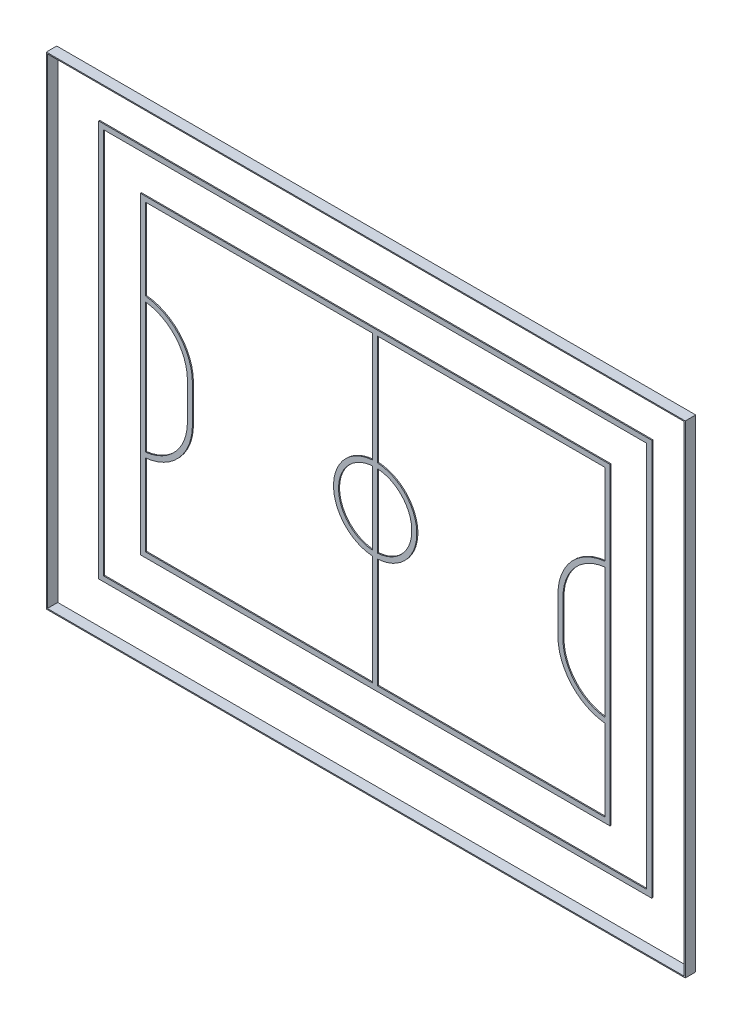
SolidWorks part; units mm, degrees
note: The reader was unsure of these and kept them because the rebuilt part matched: shared geometry of "Sketch1<3>".
ref_plane "Front Plane" through (0, 0, 0) normal (0, 0, 1) x (1, 0, 0)
ref_plane "Top Plane" through (0, 0, 0) normal (0, 1, 0) x (1, 0, 0)
ref_plane "Right Plane" through (0, 0, 0) normal (1, 0, 0) x (0, 0, -1)
sketch "Sketch1" plane through (0, 0, 0) normal (0, 0, 1) x (1, 0, 0)
  line L0 (-2250, 1500) -> (2250, 1500)
  line L1 (2250, -1500) -> (2250, 1500)
  line L2 (-2250, -1500) -> (2250, -1500)
  line L3 (-2250, -1500) -> (-2250, 1500)
  line L4 (-2251, 1501) -> (2251, 1501)
  line L5 (-2251, -1501) -> (-2251, 1501)
  line L6 (-2251, -1501) -> (2251, -1501)
  line L7 (2251, -1501) -> (2251, 1501)
  line L8 (-2200, 672.4937) -> (-2200, 1450)
  line L9 (-2200, 1450) -> (-25, 1450)
  line L10 (-25, 399.218) -> (-25, 1450)
  line L11 (-25, -1450) -> (-25, -399.218)
  line L12 (-2200, -1450) -> (-25, -1450)
  line L13 (-2200, -1450) -> (-2200, -672.4937)
  line L14 (-1750, -175) -> (-1750, 175)
  line L15 (-1751, -175) -> (-1751, 175)
  line L16 (-2201, -1451) -> (-2201, -671.5884)
  line L17 (-2201, -1451) -> (-24, -1451)
  line L18 (-24, -1451) -> (-24, -398.2775)
  line L19 (-24, 398.2775) -> (-24, 1451)
  line L20 (-2201, 1451) -> (-24, 1451)
  line L21 (-2201, 671.5884) -> (-2201, 1451)
  line L22 (-1799, -175) -> (-1799, 175)
  line L23 (-2201, -623.3302) -> (-2201, 623.3302)
  line L24 (-1800, -175) -> (-1800, 175)
  line L25 (-2200, -622.2136) -> (-2200, 622.2136)
  line L26 (-24, -350.1785) -> (-24, 350.1785)
  line L27 (-25, -349.106) -> (-25, 349.106)
  line L28 (25, -349.106) -> (25, 349.106)
  line L29 (24, -350.1785) -> (24, 350.1785)
  line L30 (2201, -1451) -> (2201, -671.5884)
  line L31 (1751, -175) -> (1751, 175)
  line L32 (2201, 671.5884) -> (2201, 1451)
  line L33 (24, 1451) -> (2201, 1451)
  line L34 (24, 398.2775) -> (24, 1451)
  line L35 (24, -1451) -> (24, -398.2775)
  line L36 (24, -1451) -> (2201, -1451)
  line L37 (2200, -1450) -> (2200, -672.4937)
  line L38 (25, -1450) -> (2200, -1450)
  line L39 (25, -1450) -> (25, -399.218)
  line L40 (25, 399.218) -> (25, 1450)
  line L41 (25, 1450) -> (2200, 1450)
  line L42 (2200, 672.4937) -> (2200, 1450)
  line L43 (1750, -175) -> (1750, 175)
  line L44 (2200, -622.2136) -> (2200, 622.2136)
  line L45 (1800, -175) -> (1800, 175)
  line L46 (1799, -175) -> (1799, 175)
  line L47 (2201, -623.3302) -> (2201, 623.3302)
  line L48 (-2600, 1850) -> (2600, 1850)
  line L49 (2600, -1850) -> (2600, 1850)
  line L50 (-2600, -1850) -> (2600, -1850)
  line L51 (-2600, -1850) -> (-2600, 1850)
  line L52 (-2601, 1851) -> (2601, 1851)
  line L53 (-2601, -1851) -> (-2601, 1851)
  line L54 (-2601, -1851) -> (2601, -1851)
  line L55 (2601, -1851) -> (2601, 1851)
  line L56 (-2650, 1900) -> (2650, 1900)
  line L57 (2650, -1900) -> (2650, 1900)
  line L58 (-2650, -1900) -> (2650, -1900)
  line L59 (-2650, -1900) -> (-2650, 1900)
  line L60 (-2651, 1901) -> (2651, 1901)
  line L61 (-2651, -1901) -> (-2651, 1901)
  line L62 (-2651, -1901) -> (2651, -1901)
  line L63 (2651, -1901) -> (2651, 1901)
  line L64 (-3050, -2300) -> (3050, -2300)
  line L65 (-3050, -2300) -> (-3050, 2300)
  line L66 (-3050, 2300) -> (3050, 2300)
  line L67 (3050, -2300) -> (3050, 2300)
  line L68 (-3051, -2301) -> (-3051, 2301)
  line L69 (-3051, -2301) -> (3051, -2301)
  line L70 (3051, -2301) -> (3051, 2301)
  line L71 (-3051, 2301) -> (3051, 2301)
  line L72 (-3061, -2311) -> (-3061, 2311)
  line L73 (-3061, 2311) -> (3061, 2311)
  line L74 (3061, -2311) -> (3061, 2311)
  line L75 (-3061, -2311) -> (3061, -2311)
  arc A0 (-1750, 175) -> (-2200, 672.4937) centre (-2250, 175) ccw
  arc A1 (-25, 399.218) -> (-25, -399.218) centre (0, 0) ccw
  arc A2 (-2200, -672.4937) -> (-1750, -175) centre (-2250, -175) ccw
  arc A3 (-1751, 175) -> (-2201, 671.5884) centre (-2250, 175) ccw
  arc A4 (-2201, -671.5884) -> (-1751, -175) centre (-2250, -175) ccw
  arc A5 (-24, 398.2775) -> (-24, -398.2775) centre (0, 0) ccw
  arc A6 (-1799, 175) -> (-2201, 623.3302) centre (-2250, 175) ccw
  arc A7 (-2201, -623.3302) -> (-1799, -175) centre (-2250, -175) ccw
  arc A8 (-1800, 175) -> (-2200, 622.2136) centre (-2250, 175) ccw
  arc A9 (-2200, -622.2136) -> (-1800, -175) centre (-2250, -175) ccw
  arc A10 (-24, 350.1785) -> (-24, -350.1785) centre (0, 0) ccw
  arc A11 (-25, 349.106) -> (-25, -349.106) centre (0, 0) ccw
  arc A12 (25, -349.106) -> (25, 349.106) centre (0, 0) ccw
  arc A13 (24, -350.1785) -> (24, 350.1785) centre (0, 0) ccw
  arc A14 (1751, -175) -> (2201, -671.5884) centre (2250, -175) ccw
  arc A15 (2201, 671.5884) -> (1751, 175) centre (2250, 175) ccw
  arc A16 (24, -398.2775) -> (24, 398.2775) centre (0, 0) ccw
  arc A17 (1750, -175) -> (2200, -672.4937) centre (2250, -175) ccw
  arc A18 (25, -399.218) -> (25, 399.218) centre (0, 0) ccw
  arc A19 (2200, 672.4937) -> (1750, 175) centre (2250, 175) ccw
  arc A20 (2200, 622.2136) -> (1800, 175) centre (2250, 175) ccw
  arc A21 (1800, -175) -> (2200, -622.2136) centre (2250, -175) ccw
  arc A22 (2201, 623.3302) -> (1799, 175) centre (2250, 175) ccw
  arc A23 (1799, -175) -> (2201, -623.3302) centre (2250, -175) ccw
  dimension "D1" = 10
extrude "Boss-Extrude1" add sketch "Sketch1" along normal blind 10 contours L3 L2 L1 L0 A23 L46 A22 L47 L19 A5 L18 L17 L16 A4 L15 A3 L21 L20 A7 L23 A6 L22 A10 L26 A13 L29 L35 A16 L34 L33 L32 A15 L31 A14 L30 L36 | L59 L58 L57 L56 L55 L54 L53 L52
extrude "Boss-Extrude2" add sketch "Sketch1<3>" along normal blind 100 separate body contours L72 L75 L74 L73 L68 L71 L70 L69
sketch "Sketch1<3>" plane through (0, 0, 0) normal (0, 0, 1) x (1, 0, 0) same geometry as "Sketch1"
